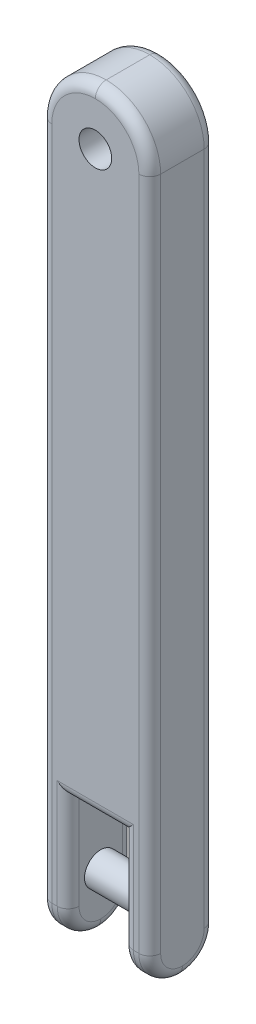
SolidWorks part; units mm, degrees
ref_plane "Alzado" through (0, 0, 0) normal (0, 0, 1) x (1, 0, 0)
ref_plane "Planta" through (0, 0, 0) normal (0, 1, 0) x (1, 0, 0)
ref_plane "Vista lateral" through (0, 0, 0) normal (1, 0, 0) x (0, 0, -1)
sketch "Croquis1" plane through (0, 0, 0) normal (0, 0, 1) x (1, 0, 0)
  line L0 (12.5, 0) -> (12.5, 60)
  line L1 (0, 0) -> (12.5, 0)
  line L2 (0, 0) -> (0, 350)
  line L3 (0, 350) -> (50, 350)
  line L4 (50, 0) -> (50, 350)
  line L5 (12.5, 60) -> (37.5, 60)
  line L6 (37.5, 60) -> (37.5, 0)
  line L7 (37.5, 0) -> (50, 0)
  circle A0 centre (25, 325) radius 7.5
  dimension "D1" = 50
  dimension "D3" = 15
  dimension "D2" = 350
  dimension "D4" = 25
  dimension "D5" = 12.5
  dimension "D6" = 60
  dimension "D7" = 12.5
extrude "Saliente-Extruir2" add sketch "Croquis1" along normal blind 30
fillet "Redondeo1" radius 25 2 edges at (0, 350, 15) (50, 350, 15)
sketch "Croquis2" plane through (0, 0, 0) normal (-1, 0, 0) x (0, 0, 1)
  circle A0 centre (15, 25) radius 7.5
extrude "Saliente-Extruir3" add sketch "Croquis2" against normal blind 50
fillet "Redondeo2" radius 5 18 edges at (37.5, 30, 0) (12.5, 30, 0) (25, 60, 0) (0, 162.5, 0) (50, 162.5, 0) (42.6777, 342.6777, 0) (7.3223, 342.6777, 0) (7.3223, 342.6777, 30) (42.6777, 342.6777, 30) (0, 162.5, 30) (50, 162.5, 30) (37.5, 30, 30) (12.5, 30, 30) (25, 60, 30) (12.5, 0, 15) (0, 0, 15) (50, 0, 15) (37.5, 0, 15)
fillet "Redondeo4" radius 15 12 edges at (48.5355, 1.4645, 1.4645) (38.9645, 1.4645, 1.4645) (11.0355, 1.4645, 1.4645) (1.4645, 1.4645, 1.4645) (11.0355, 1.4645, 28.5355) (1.4645, 1.4645, 28.5355) (48.5355, 1.4645, 28.5355) (38.9645, 1.4645, 28.5355) (43.75, 0, 30) (6.25, 0, 30) (6.25, 0, 0) (43.75, 0, 0)
